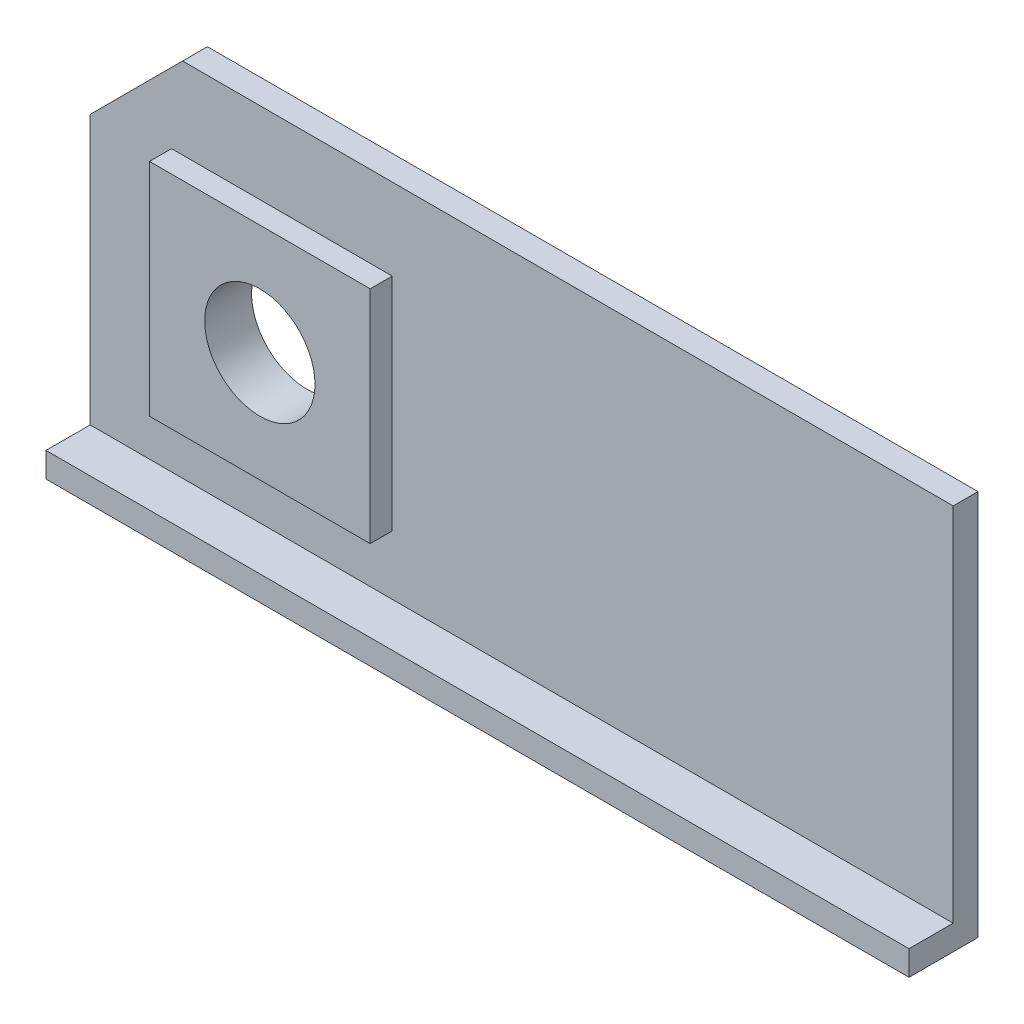
SolidWorks part; units mm, degrees
ref_plane "Front Plane" through (0, 0, 0) normal (0, 0, 1) x (1, 0, 0)
ref_plane "Top Plane" through (0, 0, 0) normal (0, 1, 0) x (1, 0, 0)
ref_plane "Right Plane" through (0, 0, 0) normal (1, 0, 0) x (0, 0, -1)
sketch "Sketch2" plane through (0, 0, 0) normal (0, 0, 1) x (-1, 0, 0)
  line L0 (6.7586, -36.6246) -> (96.7586, -36.6246)
  line L1 (96.7586, -36.6246) -> (146.4277, -36.6246)
  line L2 (146.4277, -36.6246) -> (163.1845, -19.8678)
  line L3 (163.1845, -19.8678) -> (163.1845, 33.3754)
  line L4 (163.1845, 33.3754) -> (6.7586, 33.3754)
  line L5 (6.7586, 33.3754) -> (6.7586, -36.6246)
  line L6 (96.7586, -36.6246) -> (96.7586, 28.8754)
  line L7 (6.7586, 28.8754) -> (163.1845, 28.8754)
  circle A0 centre (128.4277, -1.8678) radius 10
extrude "Boss-Extrude2" add sketch "Sketch2" along normal blind 4.5 contours L7 L6 L1 L2 L3 A0 region at (-97.6915, 3.8746, 0)
extrude "Boss-Extrude4" add sketch "Sketch2<5>" along normal blind 4.5 contours L7 L5 L0 L6 region at (-51.7586, 3.8746, 0)
sketch "Sketch2<5>" plane through (0, 0, 0) normal (0, 0, 1) x (-1, 0, 0) same geometry as "Sketch2"
extrude "Boss-Extrude5" add sketch "Sketch2<7>" along normal blind 12.5 contours L5 L7 L3 L4 region at (-84.9716, -31.1254, 0)
sketch "Sketch2<7>" plane through (0, 0, 0) normal (0, 0, 1) x (-1, 0, 0) same geometry as "Sketch2"
sketch "Sketch4" plane through (0, 0, 4.5) normal (0, 0, 1) x (1, 0, 0)
  line L4 (-108.4277, 21.8678) -> (-108.4277, -18.1322)
  line L5 (-108.4277, -18.1322) -> (-148.4277, -18.1322)
  line L6 (-148.4277, -18.1322) -> (-148.4277, 21.8678)
  line L7 (-148.4277, 21.8678) -> (-108.4277, 21.8678)
  circle A0 centre (-128.4277, 1.8678) radius 10
extrude "Boss-Extrude6" add sketch "Sketch4" along normal blind 4
